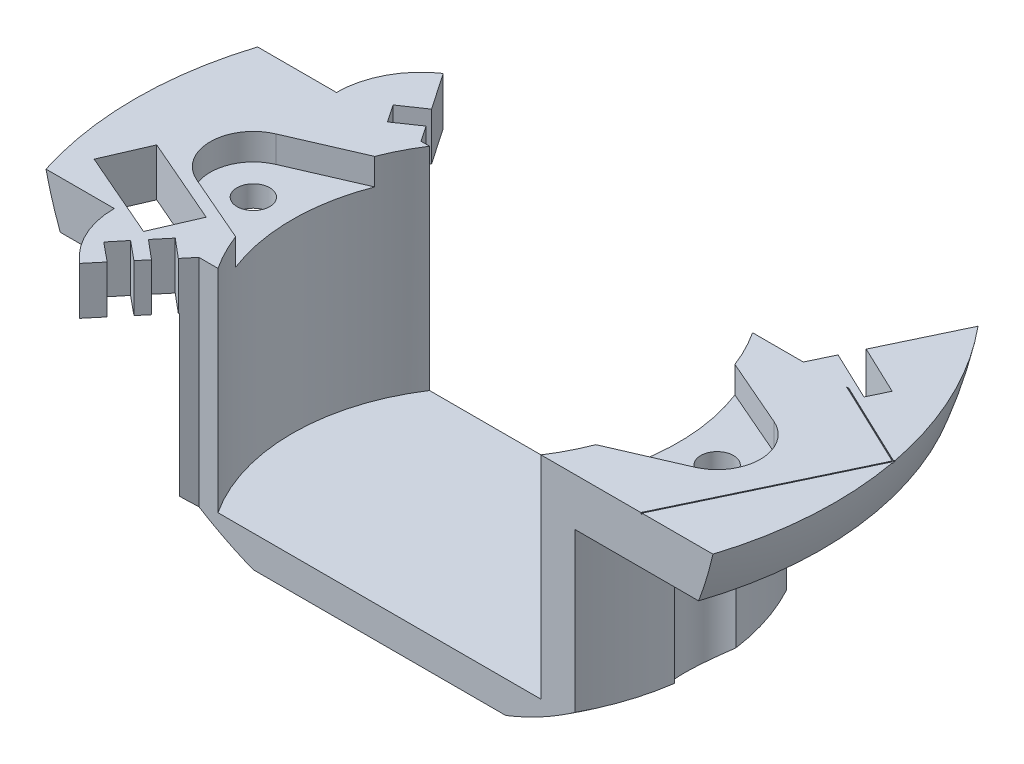
SolidWorks part; units mm, degrees
ref_plane "Front Plane" through (0, 0, 0) normal (0, 0, 1) x (1, 0, 0)
ref_plane "Top Plane" through (0, 0, 0) normal (0, 1, 0) x (1, 0, 0)
ref_plane "Right Plane" through (0, 0, 0) normal (1, 0, 0) x (0, 0, -1)
sketch "Sketch1" plane through (0, 0, 0) normal (0, 0, 1) x (1, 0, 0)
  line L0 (0, -33.8) -> (0, 0)
  line L1 (33.8, 0) -> (0, 0)
  arc A0 (0, -33.8) -> (33.8, 0) centre (0, 0) ccw
  dimension "D1" = 33.8
revolve "Revolve1" add sketch "Sketch1" angle 360 about L0
sketch "Sketch2" plane through (0, 0, 0) normal (0, 1, 0) x (1, 0, 0)
  circle A0 centre (0, 0) radius 33.8 construction
  circle A1 centre (0, 0) radius 33.8
extrude "Cut-Extrude1" cut sketch "Sketch2" against normal blind 7
sketch "Sketch3" plane through (0, -7, 0) normal (0, 1, 0) x (1, 0, 0)
  line L0 (-22.2095, -16.1284) -> (-17.0672, -10)
  line L1 (33.0672, -10) -> (-33.0672, -10)
  line L2 (33.0672, -10) -> (33.0672, 10)
  line L3 (33.0672, 10) -> (-33.0672, 10)
  line L4 (-33.0672, -10) -> (-33.0672, 10)
  line L5 (33.0672, -10) -> (-33.0672, 10) construction
  line L6 (33.0672, 10) -> (-33.0672, -10) construction
  line L7 (-17.0672, -10) -> (-25.0672, -10)
  line L8 (25.6508, 21.7398) -> (20.0672, 10)
  line L9 (21.3518, 19.8649) -> (19.2043, 15.3496) construction
  line L10 (-7.6618, 28.1274) -> (26.6546, 11.8061) construction
  line L11 (21.983, 14.028) -> (26.6546, 11.8061)
  line L12 (-8.5208, 26.3212) -> (25.7956, 10) construction
  line L13 (26.6546, 11.8061) -> (25.7956, 10) construction
  line L14 (21.1239, 12.2219) -> (25.7956, 10)
  line L15 (26.6546, 11.8061) -> (25.7956, 10)
  line L16 (-16.0672, 10) -> (-20.5791, 16.6063)
  line L17 (-24.0672, 10) -> (-16.0672, 10)
  line L18 (-17.077, 11.4786) -> (-19.242, 10)
  line L19 (-19.242, 10) -> (-2.3134, 21.5616) construction
  line L20 (-19.242, 10) -> (-20.37, 11.6516)
  line L21 (-20.37, 11.6516) -> (-18.205, 13.1302)
  line L22 (-20.37, 11.6516) -> (-16.0346, 14.6125) construction
  circle A0 centre (0, 0) radius 33.0672 construction
  arc A1 (-25.0672, -10) -> (-22.2095, -16.1284) centre (-17.0672, -10) ccw
  arc A2 (25.6508, 21.7398) -> (33.0672, 10) centre (20.0672, 10) cw
  arc A3 (-20.5791, 16.6063) -> (-24.0672, 10) centre (-16.0672, 10) ccw
  point P0 (0, 0)
  circle M5 centre (0, 0) radius 33.0672
  dimension "D1" = 20
  dimension "D2" = 16
  dimension "D3" = 50
  dimension "D4" = 8
  dimension "D5" = 13
  dimension "D6" = 17
  dimension "D7" = 8
extrude "Cut-Extrude2" cut sketch "Sketch3" against normal through all flip side to cut contours L4 L1 M5 | L3 L1 M5 | L4 L3 M5 | L2 L3 M5 | L1 L2 M5 | L1 A1 L0 | L14 L8 L3 | L11 L15 L3 L8 M5 | L16 A3 L17 L20 L21 | L16 L18 L3 region at (-21.7489, -7, 12.1831) region at (0, -7, 0) region at (32.6046, -7, 7.5119) region at (-32.6046, -7, 7.5119) region at (32.6046, -7, -7.5119) region at (-32.6046, -7, -7.5119) region at (26.7111, -7, -14.6269) region at (22.3289, -7, -10.7406) region at (-21.3323, -7, -12.768) region at (-17.4621, -7, -10.4929)
sketch "Sketch5" plane through (0, -7, 0) normal (0, 1, 0) x (1, 0, 0)
  line L0 (-21.92, 0) -> (21.92, 0) construction
  line L1 (-23.5443, 3.7427) -> (-17.0257, 6.5717)
  line L2 (-23.5443, -3.7427) -> (-17.0257, -6.5717)
  line L3 (17.0257, 6.5717) -> (23.5443, 3.7427)
  line L4 (23.5443, -3.7427) -> (17.0257, -6.5717)
  circle A0 centre (0, 0) radius 18.25
  arc A2 (-23.5443, 3.7427) -> (-23.5443, -3.7427) centre (-21.92, 0) ccw
  arc A3 (23.5443, 3.7427) -> (23.5443, -3.7427) centre (21.92, 0) cw
  point P12 (26, 0)
  point P15 (-26, 0)
  line M9 (-24.0672, 10) -> (-31.5189, 10)
  line M12 (-31.5189, -10) -> (-25.0672, -10)
  dimension "D1" = 36.5
  dimension "D2" = 43.84
  dimension "D3" = 52
  dimension "D4" = 23.46
extrude "Cut-Extrude3" cut sketch "Sketch5" against normal blind 2.5 contours L1 A2 L2 A0 | A0 L0 M9 | L0 A0 M12 | A3 L3 A0 L4 region at (0, -7, -7.7455) region at (-18.0978, -7, 3.3715) region at (0, -7, 7.7455) region at (18.0978, -7, -3.3715)
sketch "Sketch6" plane through (0, -9.5, 0) normal (0, 1, 0) x (1, 0, 0)
  circle A1 centre (0, 0) radius 18.25
  arc A2 (-15.2664, 10) -> (-17.0257, 6.5717) centre (0, 0) ccw construction
  circle A3 centre (-21.92, 0) radius 1.55
  circle A4 centre (21.92, 0) radius 1.55
  dimension "D1" = 3.1
extrude "Cut-Extrude4" cut sketch "Sketch6" against normal blind 17.5
sketch "Sketch7" plane through (0, -7, 0) normal (0, 1, 0) x (1, 0, 0)
  circle A0 centre (0, 0) radius 21
  dimension "D1" = 42
extrude "Cut-Extrude5" cut sketch "Sketch7" against normal through all from offset 4.5 flip side to cut offset against normal yes
sketch "Sketch8" plane through (0, -27, 0) normal (0, 1, 0) x (1, 0, 0)
  circle A0 centre (0, 0) radius 33.0672
  circle A2 centre (0, 0) radius 33.0672 construction
extrude "Cut-Extrude6" cut sketch "Sketch8" against normal through all from offset 3 offset against normal yes
sketch "Sketch9" plane through (0, -11.5, 0) normal (0, -1, 0) x (1, 0, 0)
  circle A0 centre (-21.92, 0) radius 3.1
  circle A1 centre (21.92, 0) radius 3.1
  dimension "D1" = 6.2
extrude "Cut-Extrude7" cut sketch "Sketch9" along normal up to next
sketch "Sketch10" plane through (0, -7, 0) normal (0, 1, 0) x (1, 0, 0)
  circle A0 centre (0, 0) radius 32.75
  circle A1 centre (0, 0) radius 26.5
  dimension "D1" = 65.5
  dimension "D2" = 53
extrude "Boss-Extrude1" [suppressed] add sketch "Sketch10" along normal blind 7 separate body
sketch "Sketch11" plane through (0, -7, 0) normal (0, 1, 0) x (1, 0, 0)
  line L0 (24.7054, -10) -> (32.359, 6.0922)
  line L1 (32.359, 6.0922) -> (24.1425, 10)
  line L2 (24.1425, 10) -> (24.3753, 10)
  line L3 (24.3753, 10) -> (32.4922, 6.1395)
  line L4 (32.4922, 6.1395) -> (24.8161, -10)
  line L5 (24.8161, -10) -> (24.7054, -10)
  line L6 (15.7415, -29.08) -> (32.4922, 6.1395) construction
  line L7 (15.2664, -10) -> (31.5189, -10) construction
  line L8 (20.0672, 10) -> (15.2664, 10) construction
  line L9 (32.4922, 6.1395) -> (10.8187, 16.4477) construction
  circle A0 centre (0, 0) radius 33.0672 construction
  circle A1 centre (32.4922, 6.1395) radius 0.1414
  line M2 (15.2664, -10) -> (31.5189, -10)
  line M5 (20.0672, 10) -> (15.2664, 10)
  dimension "D1" = 0.1
  dimension "D2" = 0.1
extrude "Cut-Extrude8" cut sketch "Sketch11" against normal blind 0.1 contours A1 L3 | L4 A1 | A1 | L3 A1 L4 | A1 L3 L1 M5 | A1 L0 L4 M2 region at (28.5763, -7, 1.9775) region at (28.3065, -7, -8.0747) region at (32.4123, -7, -6.1111) region at (32.5189, -7, -6.149)
sketch "Sketch12" plane through (0, -7, 0) normal (0, 1, 0) x (1, 0, 0)
  line L4 (-19.112, -12.4369) -> (-17.955, -11.058)
  line L5 (-19.995, -13.4892) -> (-21.8077, -12.0025)
  line L6 (-22.2095, -16.1284) -> (-17.0672, -10) construction
  line L7 (-21.8077, -12.0025) -> (-22.4418, -12.7757)
  line L8 (-22.4418, -12.7757) -> (-20.6378, -14.2553)
  line L9 (-18.9625, -15.6295) -> (-22.4418, -12.7757) construction
  line L10 (-7.8901, -23.4175) -> (-21.8077, -12.0025) construction
  line L11 (-19.995, -13.4892) -> (-20.6378, -14.2553)
  line L12 (-18.7094, -11.957) -> (-20.1527, -10.7732)
  line L13 (-20.1527, -10.7732) -> (-6.6218, -21.8711) construction
  line L14 (-20.1527, -10.7732) -> (-19.5186, -10)
  line L15 (-19.5186, -10) -> (-18.0665, -11.1909)
  line L16 (-19.5186, -10) -> (-16.2325, -12.6952) construction
  line L17 (-18.0665, -11.1909) -> (-18.7094, -11.957)
  line L18 (-19.112, -12.4369) -> (-20.9198, -10.9199)
  line L19 (-17.955, -11.058) -> (-19.7627, -9.5411)
  line L20 (-20.9198, -10.9199) -> (-19.7627, -9.5411)
  line L21 (-22.8223, -13.2396) -> (-21.6808, -11.8479)
  line L22 (-22.8223, -13.2396) -> (-20.4262, -15.2049)
  line L23 (-21.6808, -11.8479) -> (-19.2847, -13.8132)
  line L24 (-20.4262, -15.2049) -> (-19.2847, -13.8132)
  line M15 (-22.2095, -16.1284) -> (-17.0672, -10)
  dimension "D1" = 1.8
  dimension "D2" = 0.2
  dimension "D3" = 1.8
  dimension "D4" = 0.2
extrude "Cut-Extrude9" cut sketch "Sketch12" against normal through all contours L23 L21 L5 M15 | L7 L8 L5 M15 | L21 L22 L8 M15 | L22 L24 L23 M15 | L20 L18 L12 L14 L15 L19 M15 | L15 L14 L12 L4 region at (-19.9892, -7, 11.6467) region at (-20.1528, -7, 14.2703) region at (-20.8375, -7, 12.6689) region at (-19.1115, -7, 10.9799) region at (-21.2203, -7, 13.1304) region at (-21.7313, -7, 13.7463)
sketch "Sketch14" plane through (0, -7, 0) normal (0, 1, 0) x (1, 0, 0)
  line L0 (-30.0594, -6.9109) -> (-21.8034, -10.4939)
  line L1 (-30.0594, -6.9109) -> (-28.2679, -2.7829)
  line L2 (-21.8034, -10.4939) -> (-20.0119, -6.3658)
  line L3 (-28.2679, -2.7829) -> (-20.0119, -6.3658)
  line L4 (-23.5443, -3.7427) -> (-17.0257, -6.5717) construction
  arc A1 (-20.8001, -2.8906) -> (-17.8961, -10.9878) centre (0, 0) ccw construction
  point P0 (-32.111, -5.0596)
  dimension "D1" = 9
  dimension "D2" = 4.5
  dimension "D3" = 1
extrude "Cut-Extrude11" cut sketch "Sketch14" against normal through all
sketch "Sketch13" plane through (0, 0, 10) normal (0, 0, 1) x (1, 0, 0)
  line L0 (-31.7835, -11.5) -> (4.3979, -11.5)
  line L1 (-31.7835, -11.5) -> (-30.1694, -11.5) construction
  line L2 (4.3979, -11.5) -> (4.3979, 1.6571)
  line L3 (4.3979, 1.6571) -> (40.951, -1.8589)
  line L4 (40.951, -1.8589) -> (32.9239, -32.0766)
  line L5 (32.9239, -32.0766) -> (-16.3, -36.7203)
  line L6 (-16.3, -36.7203) -> (-35.3726, -23.1871)
  line L7 (-35.3726, -23.1871) -> (-31.7835, -11.5)
extrude "Cut-Extrude12" [suppressed] cut sketch "Sketch13" against normal through all both and the other way through all
